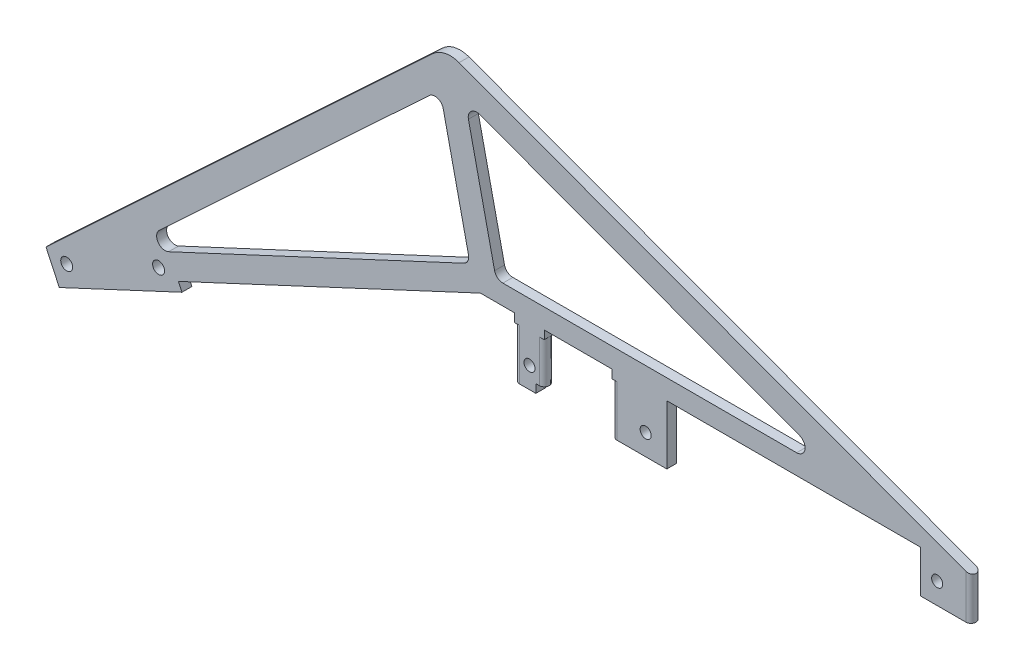
SolidWorks part; units mm, degrees
material "6061-T6 (SS)"
ref_plane "Front Plane" through (0, 0, 0) normal (0, 0, 1) x (1, 0, 0)
ref_plane "Top Plane" through (0, 0, 0) normal (0, 1, 0) x (1, 0, 0)
ref_plane "Right Plane" through (0, 0, 0) normal (1, 0, 0) x (0, 0, -1)
sketch "Sketch1" plane through (0, 0, 0) normal (0, 0, 1) x (1, 0, 0)
  line L0 (0, 0) -> (9.525, 0)
  line L1 (9.525, 0) -> (9.525, -19.05)
  line L2 (9.525, -19.05) -> (20.6375, -19.05)
  line L3 (20.6375, -19.05) -> (20.6375, 0)
  line L4 (20.6375, 0) -> (46.0375, 0)
  line L5 (46.0375, 0) -> (46.0375, -19.05)
  line L6 (46.0375, -19.05) -> (180.975, -19.05)
  line L7 (180.975, -19.05) -> (180.975, 3.175)
  line L9 (180.975, 3.175) -> (-16.8931, 76.2)
  line L10 (-16.8931, 76.2) -> (0, 0)
  point P6 (0, 0)
  point P11 (180.975, 5.8193)
  dimension "D1" = 9.525
  dimension "D2" = 11.1125
  dimension "D3" = 25.4
  dimension "D4" = 134.9375
  dimension "D5" = 19.05
  dimension "D6" = 76.2
  dimension "D7" = 102.5
  dimension "D8" = 3.175
extrude "Boss-Extrude1" add sketch "Sketch1" along normal blind 3.7338
sketch "Sketch7" plane through (0, 0, 3.7338) normal (0, 0, 1) x (1, 0, 0)
  line L0 (-0.2477, 1.1171) -> (-161.6136, -74.1291)
  line L1 (-16.8931, 76.2) -> (0, 0) construction
  line L2 (-166.6052, -63.4247) -> (-16.8931, 76.2)
  line L3 (-16.8931, 76.2) -> (-0.2477, 1.1171)
  line L4 (0, 0) -> (0, -22.225)
  line L5 (-161.6136, -74.1291) -> (-166.6052, -63.4247)
  line L6 (0, 0) -> (9.525, 0) construction
  line L7 (0, -22.225) -> (-25.8329, -34.2711)
  line L8 (-25.8329, -34.2711) -> (-34.3131, -16.0851)
  line L9 (-34.3131, -16.0851) -> (0, -0.0846)
  line M11 (-16.8931, 76.2) -> (0, 0)
  dimension "D2" = 11.811
  dimension "D3" = 177.8
  dimension "D4" = 205
  dimension "D5" = 20.066
  dimension "D6" = 22.225
  dimension "D1" = 1.1938
extrude "Boss-Extrude2" add sketch "Sketch7" against normal up to surface (3.7338 mm away) contours L0 M11 region at (-67.7234, -2.0949, 3.7338) up to face at (49.7457, 0.3175, 0)
sketch "Sketch8" plane through (0, 0, 3.7338) normal (0, 0, 1) x (1, 0, 0)
  line L0 (-2.1125, 9.5289) -> (-8.5131, 38.4) construction
  line L1 (180.975, 3.175) -> (-16.8931, 76.2) construction
  line L2 (-166.6052, -63.4247) -> (-16.8931, 76.2) construction
  line L3 (-0.2477, 1.1171) -> (-161.6136, -74.1291) construction
  line L4 (180.975, 3.175) -> (-16.8931, 76.2) construction
  line L13 (2.5188, 10.6421) -> (133.2317, 10.6421)
  line L16 (-18.5427, 61.6371) -> (-138.6745, -50.4004)
  line L17 (133.2317, 10.6421) -> (-9.1289, 63.1816)
  line L19 (-7.2872, 10.8665) -> (-138.6745, -50.4004)
  line L22 (-2.3593, 10.6421) -> (-10.0114, 45.1587) construction
  line L23 (2.5188, 10.6421) -> (-9.1289, 63.1816)
  line L24 (-7.2872, 10.8665) -> (-18.5427, 61.6371)
  line L26 (2.5371, 10.5597) -> (-3.8635, 39.4308) construction
  line L27 (-6.7621, 8.4981) -> (-13.1627, 37.3692) construction
  dimension "D3" = 9.525
  dimension "D6" = 9.525
  dimension "D1" = 9.525
  dimension "D2" = 11.811
  dimension "D4" = 4.7625
  dimension "D5" = 4.7625
extrude "Cut-Extrude1" cut sketch "Sketch8" against normal through all
fillet "Fillet7" radius 9.525 1 edges at (-16.8931, 76.2, 1.8669)
fillet "Fillet8" radius 3.175 6 edges at (-138.6745, -50.4004, 1.8669) (133.2317, 10.6421, 1.8669) (-7.2872, 10.8665, 1.8669) (2.5188, 10.6421, 1.8669) (-9.1289, 63.1816, 1.8669) (-18.5427, 61.6371, 1.8669)
hole_wizard "#8-32 Tapped Hole2" positions "Sketch5" profile "Sketch6" tap size "#8-32" standard "ANSI Inch" end condition through all
sketch "Sketch5" plane through (0, 0, 3.7338) normal (0, 0, 1) x (1, 0, 0)
  line L0 (9.525, -11.1125) -> (20.6375, -11.1125)
  line L1 (9.525, 0) -> (9.525, -19.05) construction
  line L2 (180.975, -19.05) -> (180.975, 3.175) construction
  line L4 (0, 0) -> (9.525, 0) construction
  line L5 (20.6375, -11.1125) -> (180.975, -11.1125)
  line L6 (20.6375, -19.05) -> (20.6375, 0) construction
  line L7 (46.0375, 0) -> (46.0375, -19.05) construction
  point P0 (15.0813, -11.1125)
  point P2 (58.7375, -11.1125)
  point P4 (168.275, -4.7625)
  dimension "D1" = 11.1125
  dimension "D2" = 12.7
  dimension "D3" = 12.7
  dimension "D4" = 7.9375
sketch "Sketch6" plane through (15.0813, -11.1125, 3.7338) normal (1, 0, 0) x (0, -1, 0)
  line L0 (0, 0) -> (0, 3.7338)
  line L1 (0, 3.7338) -> (2.0828, 3.7338)
  line L2 (2.0828, 3.7338) -> (2.0828, 0)
  line L5 (2.0828, 0) -> (0, 0)
  line L11 (0, -6.35) -> (0, 107.95) construction
  dimension "Thread Major Dia." = 4.1656
  dimension "Thru Tap Drill Depth" = 3.7338
fillet "Fillet3" 2 edges at (9.525, -9.525, 3.7338) (9.525, -9.525, 0) type full round first side face at (17.164, -11.1125, 3.7338) second side face at (17.164, -11.1125, 0) middle face at (9.525, -9.525, 1.8669)
fillet "Fillet4" 2 edges at (20.6375, -9.525, 0) (20.6375, -9.525, 3.7338) type full round first side face at (17.164, -11.1125, 0) second side face at (17.164, -11.1125, 3.7338) middle face at (20.6375, -9.525, 1.8669)
fillet "Fillet5" 2 edges at (46.0375, -9.525, 3.7338) (46.0375, -9.525, 0) type full round first side face at (17.164, -11.1125, 3.7338) second side face at (17.164, -11.1125, 0) middle face at (46.0375, -9.525, 1.8669)
fillet "Fillet6" 2 edges at (180.975, -7.9375, 0) (180.975, -7.9375, 3.7338) type full round first side face at (17.164, -11.1125, 0) second side face at (17.164, -11.1125, 3.7338) middle face at (180.975, -7.9375, 1.8669)
hole_wizard "#8 Clearance Hole1" positions "Sketch10" profile "Sketch11" hole size "#8" standard "ANSI Inch" end condition through all
sketch "Sketch10" plane through (0, 0, 3.7338) normal (0, 0, 1) x (1, 0, 0)
  line L1 (-164.5849, -67.7571) -> (-124.2996, -48.9717)
  line L6 (-0.2477, 1.1171) -> (-161.6136, -74.1291) construction
  line L9 (-161.6136, -74.1291) -> (-166.6052, -63.4247) construction
  point P0 (-158.8299, -65.0735)
  point P2 (-124.2996, -48.9717)
  dimension "D1" = 6.35
  dimension "D2" = 38.1
  dimension "D3" = 7.0307
sketch "Sketch11" plane through (-158.8299, -65.0735, 3.7338) normal (1, 0, 0) x (0, -1, 0)
  line L0 (0, 0) -> (0, 3.7338)
  line L1 (0, 3.7338) -> (2.2479, 3.7338)
  line L2 (2.2479, 3.7338) -> (2.2479, 0)
  line L5 (2.2479, 0) -> (0, 0)
  line L11 (0, -6.35) -> (0, 107.95) construction
  dimension "Thru Hole Dia." = 4.4958
  dimension "Thru Hole Depth" = 3.7338
sketch "Sketch12" plane through (0, 0, 3.7338) normal (0, 0, 1) x (1, 0, 0)
  line L0 (-0.2477, 1.1171) -> (0, 1.2326)
  line L1 (0, 1.2326) -> (0, 0)
  line L2 (0, 0) -> (-0.2477, 1.1171)
  line L3 (-0.2477, 1.1171) -> (-161.6136, -74.1291) construction
extrude "Cut-Extrude2" cut sketch "Sketch12" against normal through all
sketch "Sketch13" [suppressed] plane through (0, 0, 4.7625) normal (0, 0, 1) x (1, 0, 0)
  line L0 (164.9832, 107.4851) -> (191.6837, -42.5578)
  line L5 (164.9832, 107.4851) -> (-202.3311, 42.1207)
  line L6 (191.6837, -42.5578) -> (-175.6307, -107.9221)
  line L7 (-202.3311, 42.1207) -> (-175.6307, -107.9221)
  arc A0 (-11.3449, 74.0803) -> (-21.2381, 72.1507) centre (-14.7442, 65.1826) ccw construction
  dimension "D1" = 10.16
  dimension "D2" = 1.524
  dimension "D3" = 152.4
sketch "Sketch14" plane through (0, 0, 3.7338) normal (0, 0, 1) x (1, 0, 0)
  line L0 (71.4375, -11.1125) -> (157.2765, -11.1125) construction
  line L1 (71.4375, -6.35) -> (157.2765, -6.35)
  line L2 (71.4375, -15.875) -> (157.2765, -15.875)
  line L3 (47.9044, -19.05) -> (179.1081, -19.05) construction
  arc A0 (71.4375, -6.35) -> (71.4375, -15.875) centre (71.4375, -11.1125) ccw
  arc A1 (157.2765, -15.875) -> (157.2765, -6.35) centre (157.2765, -11.1125) ccw
  circle A2 centre (58.7375, -11.1125) radius 2.0828 construction
  circle A3 centre (58.7375, -11.1125) radius 2.0828 construction
  circle A4 centre (168.275, -4.7625) radius 2.0828 construction
  point P2 (114.357, -11.1125)
  dimension "D1" = 3.175
  dimension "D2" = 12.7
  dimension "D3" = 12.7
extrude "Cut-Extrude3" cut sketch "Sketch14" against normal through all contours L1 A1 L2 A0
sketch "Sketch15" plane through (0, 0, 3.7338) normal (0, 0, 1) x (1, 0, 0)
  line L0 (66.675, -11.1125) -> (66.675, -19.05)
  line L1 (47.9044, -19.05) -> (179.1081, -19.05) construction
  line L2 (66.675, -19.05) -> (162.039, -19.05)
  line L3 (162.039, -19.05) -> (162.039, -11.1125)
  line L4 (162.039, -11.1125) -> (66.675, -11.1125)
  arc A0 (71.4375, -6.35) -> (71.4375, -15.875) centre (71.4375, -11.1125) ccw construction
  arc A1 (157.2765, -15.875) -> (157.2765, -6.35) centre (157.2765, -11.1125) ccw construction
extrude "Cut-Extrude4" cut sketch "Sketch15" against normal through all
sketch "Sketch16" plane through (0, 0, 3.7338) normal (0, 0, 1) x (1, 0, 0)
  line L0 (162.039, -19.05) -> (162.039, -11.1125) construction
  line L1 (162.039, -12.7) -> (180.975, -12.7)
  line L2 (162.039, -12.7) -> (162.039, -19.05)
  line L3 (162.039, -19.05) -> (180.975, -19.05)
  line L4 (180.975, -12.7) -> (180.975, -19.05)
  dimension "D1" = 6.35
extrude "Cut-Extrude5" cut sketch "Sketch16" against normal through all
sketch "Sketch17" plane through (0, 0, 3.7338) normal (0, 0, 1) x (1, 0, 0)
  line L0 (11.3919, -19.05) -> (18.7706, -19.05) construction
  line L1 (17.4625, -19.05) -> (20.6375, -19.05)
  line L2 (17.4625, -19.05) -> (17.4625, -15.875)
  line L3 (17.4625, -15.875) -> (20.6375, -15.875)
  line L4 (20.6375, -19.05) -> (20.6375, -15.875)
  line L5 (20.6375, -19.05) -> (20.6375, 0) construction
  dimension "D1" = 3.175
  dimension "D2" = 3.175
extrude "Cut-Extrude6" cut sketch "Sketch17" against normal through all both and the other way through all
sketch "Sketch18" plane through (0, 0, 3.7338) normal (0, 0, 1) x (1, 0, 0)
  line L0 (66.675, -11.1125) -> (66.675, -19.05) construction
  line L1 (162.039, -12.7) -> (66.675, -12.7)
  line L2 (162.039, -12.7) -> (162.039, 3.175)
  line L3 (162.039, 3.175) -> (66.675, 3.175)
  line L4 (66.675, -12.7) -> (66.675, 3.175)
  line L5 (18.7706, 0) -> (47.9044, 0) construction
  line L6 (20.6375, -15.875) -> (20.6375, 0) construction
  line L7 (46.0375, 0) -> (20.6375, 0)
  line L8 (46.0375, 0) -> (46.0375, 3.175)
  line L9 (46.0375, 3.175) -> (20.6375, 3.175)
  line L10 (20.6375, 0) -> (20.6375, 3.175)
  line L11 (46.0375, 0) -> (46.0375, -19.05) construction
  line L12 (-115.5183, -52.6345) -> (-2.0054, 0.2975)
  line L13 (-115.5183, -52.6345) -> (-116.8601, -49.7569)
  line L14 (-2.0054, 0.2975) -> (-3.3472, 3.175)
  line L15 (-116.8601, -49.7569) -> (-3.3472, 3.175)
  line L16 (0, 1.2326) -> (-161.6136, -74.1291) construction
  line L17 (9.525, 0) -> (9.525, 3.175)
  line L18 (0, 0) -> (11.3919, 0) construction
  line L19 (9.525, 3.175) -> (-3.3472, 3.175)
  line L20 (-2.0054, 0.2975) -> (0, 1.2326)
  line L21 (0, 1.2326) -> (0, 0)
  line L22 (0, 0) -> (9.525, 0)
  line L23 (9.525, 0) -> (9.525, -19.05) construction
  line M8 (18.7706, 0) -> (47.9044, 0)
  arc M12 (66.675, -11.1125) -> (71.4375, -6.35) centre (71.4375, -11.1125) cw
  line M13 (71.4375, -6.35) -> (157.2765, -6.35)
  arc M14 (157.2765, -6.35) -> (162.039, -11.1125) centre (157.2765, -11.1125) cw
  line M22 (-161.6136, -74.1291) -> (0, 1.2326)
  line M23 (0, 1.2326) -> (0, 0)
  line M24 (0, 0) -> (11.3919, 0)
  dimension "D1" = 3.175
  dimension "D2" = 3.175
extrude "Cut-Extrude7" cut sketch "Sketch18" against normal through all contours L17 L19 L14 M22 M23 M24 | L15 L13 L14 M22 | L10 L8 L9 M8 | L4 L2 L3 M12 M13 M14 region at (114.357, -1.6493, 3.7338) region at (33.3375, 1.5875, 3.7338) region at (-59.4327, -24.7297, 3.7338) region at (3.6247, 1.6683, 3.7338)
equation "\"D1@Sketch7\"=(.884-.79)/2"
